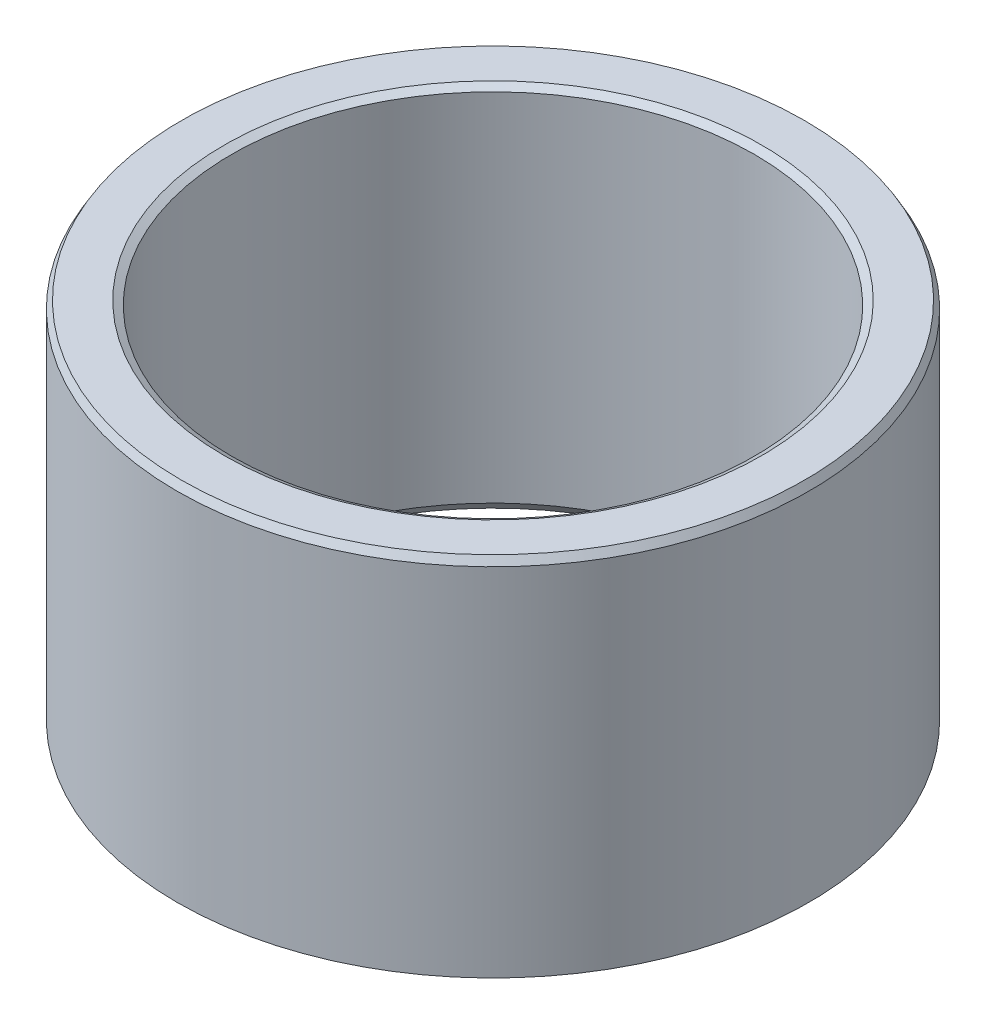
SolidWorks part; units mm, degrees
ref_plane "Front Plane" through (0, 0, 0) normal (0, 0, 1) x (1, 0, 0)
ref_plane "Top Plane" through (0, 0, 0) normal (0, 1, 0) x (1, 0, 0)
ref_plane "Right Plane" through (0, 0, 0) normal (1, 0, 0) x (0, 0, -1)
sketch "Sketch1" plane through (0, 0, 0) normal (0, 1, 0) x (1, 0, 0)
  circle A0 centre (0, 0) radius 45
  dimension "SLEEVE_OD" = 90
extrude "Boss-Extrude1" add sketch "Sketch1" along normal blind 52.4145
sketch "Sketch2" plane through (0, 0, 0) normal (0, 1, 0) x (1, 0, 0)
  circle A0 centre (0, 0) radius 37.2503
  dimension "BORE_D" = 74.5005
extrude "Cut-Extrude1" cut sketch "Sketch2" along normal through all
chamfer "Chamfer1" distance 1.0606 angle 30 4 edges at (0, 52.4145, 37.2503) (0, 0, 37.2503) (0, 0, 45) (0, 52.4145, 45) first distance on face at (0, 52.4145, 37.2503) first distance on face at (0, 0, 37.2503) first distance on face at (0, 52.4145, 45)
